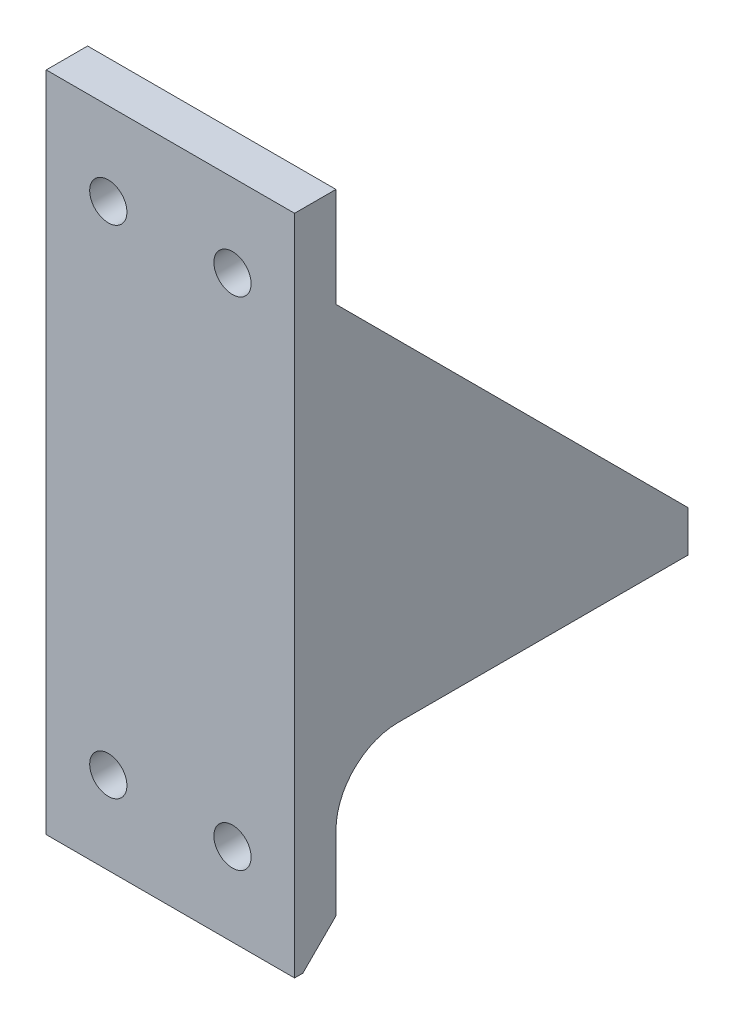
SolidWorks part; units mm, degrees
ref_plane "Front Plane" through (0, 0, 0) normal (0, 0, 1) x (1, 0, 0)
ref_plane "Top Plane" through (0, 0, 0) normal (0, 1, 0) x (1, 0, 0)
ref_plane "Right Plane" through (0, 0, 0) normal (1, 0, 0) x (0, 0, -1)
sketch "Sketch1" plane through (0, 0, 0) normal (0, 0, 1) x (1, 0, 0)
  line L5 (-30, -80) -> (30, -80)
  line L6 (-30, -80) -> (-30, 80)
  line L7 (-30, 80) -> (30, 80)
  line L8 (30, -80) -> (30, 80)
  line L9 (-30, -80) -> (30, 80) construction
  line L10 (-30, 80) -> (30, -80) construction
  point P0 (0, 0)
  dimension "D1" = 160
  dimension "D2" = 60
extrude "Boss-Extrude1" add sketch "Sketch1" along normal blind 10
sketch "Sketch2" plane through (0, 0, 0) normal (1, 0, 0) x (0, 0, -1)
  line L0 (0, -80) -> (0, 80) construction
  line L2 (0, -29.048) -> (0, -39.048)
  line L3 (0, -39.048) -> (85, -39.048)
  line L4 (85, -29.048) -> (85, -39.048)
  line L6 (-5, -80) -> (-5, -60) construction
  line L7 (-10, -80) -> (0, -80) construction
  line L8 (-5, -117.628) -> (-5, -60) construction
  line L9 (-5, -117.628) -> (85, -117.628) construction
  line L10 (85, -29.048) -> (0, 55.952)
  line L11 (0, -29.048) -> (0, 55.952)
  dimension "D1" = 10
  dimension "D2" = 20
  dimension "D4" = 78.58
  dimension "D5" = 85
  dimension "D6" = 45
  dimension "D3" = 57.628
extrude "Boss-Extrude2" add sketch "Sketch2" along normal up to surface and the other way up to surface up to face at (30, 0, 5) other way up to face at (-30, 0, 5)
sketch "Sketch3" plane through (0, -39.048, 0) normal (0, -1, 0) x (1, 0, 0)
  line L1 (-10.3187, -34.7563) -> (10.3188, -34.7563) construction
  line L2 (-10.3187, -34.7563) -> (-10.3187, -74.4438) construction
  line L3 (-10.3187, -74.4438) -> (10.3188, -74.4438) construction
  line L4 (10.3188, -34.7563) -> (10.3188, -74.4438) construction
  line L5 (-10.3187, -34.7563) -> (10.3188, -74.4438) construction
  line L6 (-10.3187, -74.4438) -> (10.3188, -34.7563) construction
  line L7 (-15.0813, -80) -> (15.0812, -80) construction
  line L8 (-15.0813, -80) -> (-15.0813, -29.2) construction
  line L9 (-15.0813, -29.2) -> (15.0812, -29.2) construction
  line L10 (15.0812, -80) -> (15.0812, -29.2) construction
  line L11 (-15.0813, -80) -> (15.0812, -29.2) construction
  line L12 (-15.0813, -29.2) -> (15.0812, -80) construction
  line L13 (30, -85) -> (-30, -85) construction
  circle A0 centre (-10.3187, -34.7563) radius 2.38
  circle A1 centre (10.3188, -34.7563) radius 2.38
  circle A2 centre (10.3188, -74.4438) radius 2.38
  circle A3 centre (-10.3187, -74.4438) radius 2.38
  point P0 (0, -54.6)
  point P10 (0, -54.6)
  dimension "D3" = 4.76
  dimension "D1" = 20.6375
  dimension "D2" = 39.6875
  dimension "D4" = 50.8
  dimension "D5" = 30.1625
  dimension "D6" = 5
extrude "Cut-Extrude1" cut sketch "Sketch3" against normal up to next
chamfer "Chamfer1" distance 8 angle 45 1 edges at (0, -80, 0)
sketch "Sketch4" plane through (0, 0, 0) normal (0, 0, -1) x (-1, 0, 0)
  line L0 (-30, 60) -> (30, 60) construction
  line L1 (-30, 55.952) -> (-30, 80) construction
  line L2 (30, 80) -> (30, 55.952) construction
  line L3 (-30, 80) -> (30, 80) construction
  line L4 (30, -60) -> (-30, -60) construction
  line L5 (30, -39.048) -> (30, -72) construction
  line L6 (-30, -72) -> (-30, -39.048) construction
  line L7 (30, -80) -> (-30, -80) construction
  circle A0 centre (-15, -60) radius 4.5
  circle A1 centre (15, -60) radius 4.5
  circle A2 centre (-15, 60) radius 4.5
  circle A3 centre (15, 60) radius 4.5
  dimension "D2" = 20
  dimension "D3" = 9
  dimension "D1" = 20
  dimension "D4" = 30
  dimension "D5" = 15
extrude "Cut-Extrude2" cut sketch "Sketch4" against normal up to next
sketch "Sketch5" plane through (0, 80, 0) normal (0, 1, 0) x (1, 0, 0)
  circle A0 centre (-10.3187, 74.4438) radius 7.5
  circle A1 centre (10.3188, 74.4438) radius 7.5
  circle A2 centre (-10.3187, 34.7563) radius 7.5
  circle A3 centre (10.3188, 34.7563) radius 7.5
  dimension "D1" = 15
extrude "Cut-Extrude4" cut sketch "Sketch5" against normal offset from surface (114.048 mm away) 5 contours A2 | A0 | A1 | A3 up to face at (-10.3187, -39.048, -37.1363)
sketch "Sketch6" plane through (0, 0, 0) normal (0, 0, -1) x (-1, 0, 0)
  circle A0 centre (-15, 60) radius 7.5
  circle A1 centre (15, 60) radius 7.5
  dimension "D1" = 15
extrude "Cut-Extrude5" cut sketch "Sketch6" along normal blind 5
fillet "Fillet1" radius 15 1 edges at (0, -39.048, 0)
equation "\"Thicknes\"=10"
equation "\"D1@Sketch2\"=\"Thicknes\""
equation "\"D1@Sketch3\"=20.6375"
equation "\"D5@Sketch4\"=\"D4@Sketch4\"/2"
